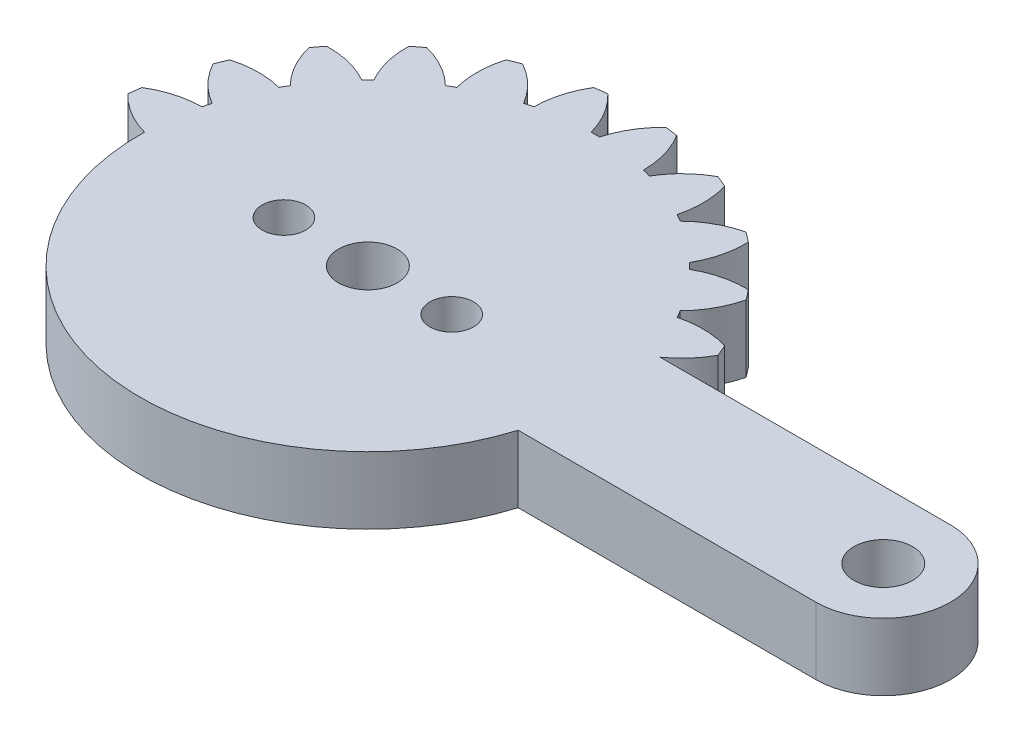
SolidWorks part; units mm, degrees
ref_plane "Ön Düzlem" through (0, 0, 0) normal (0, 0, 1) x (1, 0, 0)
ref_plane "Üst Düzlem" through (0, 0, 0) normal (0, 1, 0) x (1, 0, 0)
ref_plane "Sağ Düzlem" through (0, 0, 0) normal (1, 0, 0) x (0, 0, -1)
sketch "Çizim1" plane through (0, 0, 0) normal (0, 1, 0) x (1, 0, 0)
  line L0 (-55, 0) -> (55, 0) construction
  line L3 (0, 15.9439) -> (0, 10.0716)
  line L4 (0, -55) -> (0, 55) construction
  arc A0 (1.7298, 16.037) -> (-1.7298, 16.037) centre (0, 0) ccw
  arc A1 (0.25, 13.5627) -> (-0.25, 13.5627) centre (0, 0) ccw
  circle A2 centre (0, 0) radius 1.75
  circle A3 centre (-5, 0) radius 1.3
  circle A4 centre (5, 0) radius 1.3
  arc A5 (-0.25, 13.5627) -> (-1.7298, 16.037) centre (-5.4561, 12.1287) ccw
  arc A6 (0.25, 13.5627) -> (1.7298, 16.037) centre (5.4561, 12.1287) cw
  dimension "D1" = 32.26
  dimension "D2" = 27.13
  dimension "D3" = 3.5
  dimension "D4" = 2.6
  dimension "D5" = 2.6
  dimension "D8" = 10.8
  dimension "D9" = 0.5
  dimension "D6" = 10
  dimension "D7" = 5
sketch "Çizim2" plane through (0, 0, 0) normal (0, 1, 0) x (1, 0, 0)
  circle A0 centre (0, 0) radius 1.75
  circle A1 centre (5, 0) radius 1.3
  circle A2 centre (-5, 0) radius 1.2999
  circle A3 centre (0, 0) radius 16.13
  dimension "D1" = 32.26
extrude "Yükseklik-Ekstrüzyon1" add sketch "Çizim2" along normal blind 4
extrude "Kes-Ekstrüzyon2" cut sketch "Çizim1" along normal blind 4 contours A1 A6 A0 L3 | A5 A1 L3 A0 region at (0.7848, 0, -14.9225)
pattern_circular "Dairesel Kaplama2" count 24 over 360 about axis through (0, 4, 0) along (0, 1, 0) of "Kes-Ekstrüzyon2"
sketch "Çizim4" plane through (0, 0, 0) normal (0, 1, 0) x (1, 0, 0)
  line L2 (11.3826, 4) -> (22.8585, 4)
  line L3 (11.3826, -4) -> (22.3917, -4)
  line L4 (22.8585, 4) -> (30.7226, 4)
  line L5 (22.3917, -4) -> (30.7226, -4)
  arc A0 (11.3826, -4) -> (11.3826, 4) centre (0, 0) ccw
  circle A1 centre (30.7226, 0) radius 1.75
  arc A2 (30.7226, -4) -> (30.7226, 4) centre (30.7226, 0) ccw
  dimension "D3" = 3.5
  dimension "D1" = 8
  dimension "D2" = 19.34
extrude "Yükseklik-Ekstrüzyon2" add sketch "Çizim4" along normal blind 4
sketch "Çizim5" plane through (0, 0, 0) normal (0, 1, 0) x (1, 0, 0)
  line L0 (-13.565, 0) -> (-18.5294, 0)
  line L1 (-55, 0) -> (55, 0) construction
  line L2 (-18.5294, 0) -> (-18.5294, -18.2112)
  line L3 (-18.5294, -18.2112) -> (15.6616, -18.5769)
  line L4 (15.6616, -18.5769) -> (15.6616, -4)
  line L5 (13.4206, -4) -> (30.7226, -4) construction
  line L6 (15.6616, -4) -> (12.9618, -4)
  arc A0 (-13.565, 0) -> (12.9618, -4) centre (0, 0) ccw
extrude "Kes-Ekstrüzyon3" cut sketch "Çizim5" along normal blind 4
